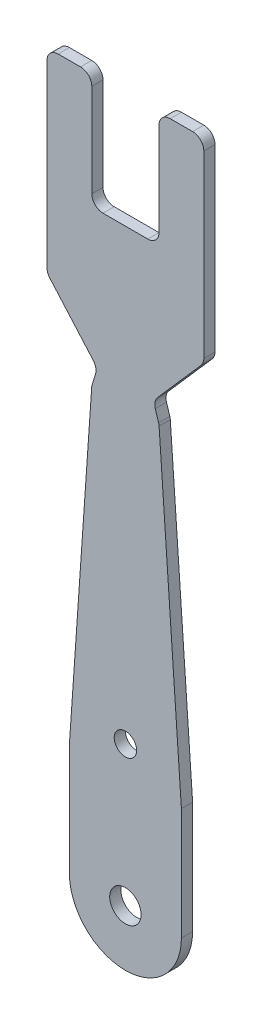
SolidWorks part; units mm, degrees
ref_plane "Alzado" through (0, 0, 0) normal (0, 0, 1) x (1, 0, 0)
ref_plane "Planta" through (0, 0, 0) normal (0, 1, 0) x (1, 0, 0)
ref_plane "Vista lateral" through (0, 0, 0) normal (1, 0, 0) x (0, 0, -1)
sketch "Model" plane through (0, 0, 0) normal (0, 0, 1) x (1, 0, 0)
  line L0 (40.206, -5.7616) -> (42.1979, 22.8197)
  line L1 (50.206, -15.7616) -> (40.206, -15.7616) construction
  line L2 (50.206, -5.7616) -> (50.206, -15.7616)
  line L3 (50.206, -5.7616) -> (48.2141, 22.8197)
  line L4 (42.2409, 23.0482) -> (42.5389, 24.0031)
  line L5 (42.3364, 24.9601) -> (38.4539, 29.3907)
  line L6 (38.206, 30.0497) -> (38.206, 46.0853)
  line L7 (39.206, 47.0853) -> (41.206, 47.0853)
  line L8 (40.206, -5.7616) -> (40.206, -15.7616)
  line L9 (42.206, 46.0853) -> (42.206, 37.7781)
  line L10 (43.206, 36.7781) -> (47.206, 36.7781)
  line L11 (48.206, 37.7781) -> (48.206, 46.0853)
  line L12 (49.206, 47.0853) -> (51.206, 47.0853)
  line L13 (52.206, 46.0853) -> (52.206, 30.0497)
  line L14 (51.9581, 29.3907) -> (48.0756, 24.9601)
  line L15 (45.206, -2.0116) -> (45.206, 22.9884) construction
  line L16 (47.706, 10.4884) -> (55.206, 10.4884) construction
  line L17 (47.8731, 24.0031) -> (48.1711, 23.0482)
  line L18 (42.206, 22.9365) -> (48.206, 22.9365) construction
  line L19 (42.706, 24.5383) -> (47.706, 24.5383) construction
  arc A0 (48.0756, 24.9601) -> (47.8731, 24.0031) centre (48.8276, 24.301) ccw
  arc A1 (40.206, -15.7616) -> (50.206, -15.7616) centre (45.206, -15.7616) ccw
  arc A2 (48.2141, 22.8197) -> (48.1711, 23.0482) centre (47.2165, 22.7502) ccw
  arc A3 (42.1979, 22.8197) -> (42.2409, 23.0482) centre (43.1954, 22.7502) cw
  arc A4 (42.5389, 24.0031) -> (42.3364, 24.9601) centre (41.5843, 24.301) ccw
  circle A5 centre (45.206, -15.7616) radius 1.4
  circle A6 centre (45.206, -3.2616) radius 1
  arc A7 (38.206, 30.0497) -> (38.4539, 29.3907) centre (39.206, 30.0497) ccw
  arc A8 (51.9581, 29.3907) -> (52.206, 30.0497) centre (51.206, 30.0497) ccw
  arc A9 (52.206, 46.0853) -> (51.206, 47.0853) centre (51.206, 46.0853) ccw
  arc A10 (48.206, 46.0853) -> (49.206, 47.0853) centre (49.206, 46.0853) cw
  arc A11 (48.206, 37.7781) -> (47.206, 36.7781) centre (47.206, 37.7781) cw
  arc A12 (43.206, 36.7781) -> (42.206, 37.7781) centre (43.206, 37.7781) cw
  arc A13 (42.206, 46.0853) -> (41.206, 47.0853) centre (41.206, 46.0853) ccw
  arc A14 (39.206, 47.0853) -> (38.206, 46.0853) centre (39.206, 46.0853) ccw
  dimension "D1" = 3
  dimension "D2" = 12.5
  dimension "D3" = 10
  dimension "D4" = 2.5
  dimension "D5" = 6
  dimension "D6" = 3
  dimension "D7" = 14
  dimension "D8" = 7
  dimension "D11" = 1
  dimension "D9" = 2.5
  dimension "D10" = 3
  dimension "D12" = 10
base flange "Brida base1" sketch "Model" thickness 1 reverse thickness direction no parameters "D1"=0.7366
sketch "Líneas de pliegue1" [suppressed] plane through (0, 0, 0) normal (0, 1, 0) x (1, 0, 0)
sketch "Cuadro delimitador1" [suppressed] plane through (0, 0, 0) normal (0, 1, 0) x (1, 0, 0)
sheet metal parameters "Chapa metálica1" thickness 1 parameters "D1"=0.7366
flat pattern "Chapa desplegada1" [suppressed]
sketch "Líneas de pliegue2" plane through (0, 0, 0) normal (0, 0, 1) x (1, 0, 0)
sketch3d "Cuadro delimitador2" [suppressed]
  line L0 (3.3783, 22.7842, 0) -> (3.3783, -45.0624, 0) construction
  line L1 (-10.6217, 22.7842, 0) -> (-10.6217, -45.0624, 0) construction
  line L2 (3.3783, 22.7842, 0) -> (-10.6217, 22.7842, 0) construction
  line L3 (3.3783, -45.0624, 0) -> (-10.6217, -45.0624, 0) construction
